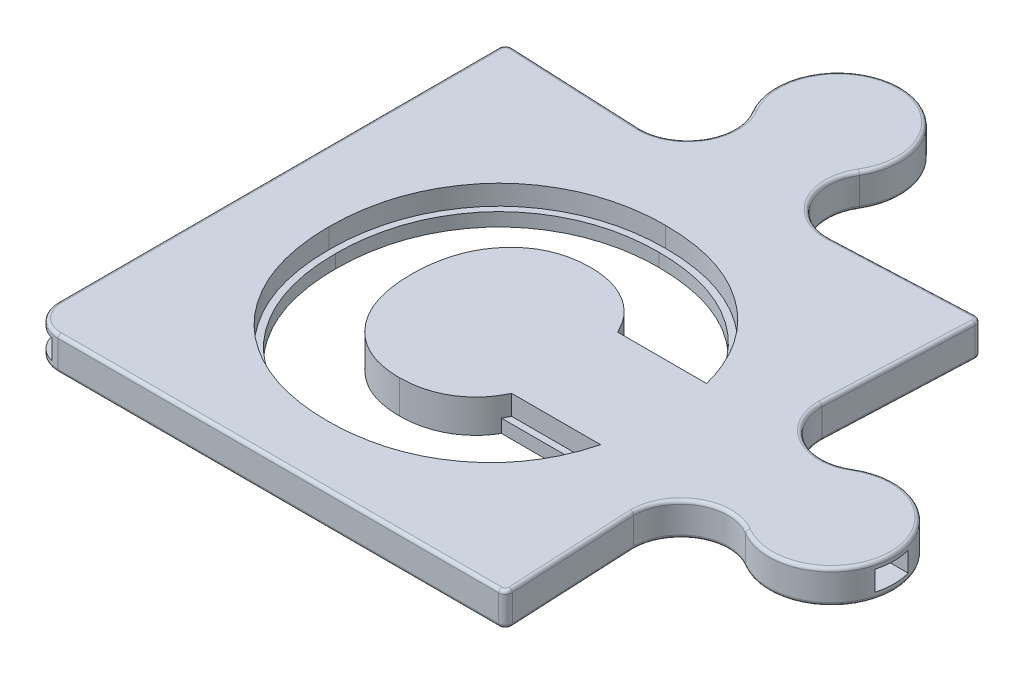
SolidWorks part; units mm, degrees
ref_plane "Front Plane" through (0, 0, 0) normal (0, 0, 1) x (1, 0, 0)
ref_plane "Top Plane" through (0, 0, 0) normal (0, 1, 0) x (1, 0, 0)
ref_plane "Right Plane" through (0, 0, 0) normal (1, 0, 0) x (0, 0, -1)
sketch "Sketch1" plane through (0, 0, 0) normal (0, 1, 0) x (1, 0, 0)
  line L0 (-31, -36) -> (37, -36) construction
  line L1 (-36, 37) -> (-36, -31) construction
  line L2 (-14.1421, 36) -> (-36, 37) construction
  line L3 (37, 37) -> (14.1421, 36) construction
  line L4 (36, 13.1421) -> (37, 37) construction
  line L5 (37, -36) -> (36, -15.1421) construction
  line L6 (-35.4, 36.3719) -> (-35.4, -31)
  line L7 (-36, 36) -> (36, 36) construction
  line L8 (-36, 36) -> (-36, -36) construction
  line L9 (-36, -36) -> (36, -36) construction
  line L10 (36, 36) -> (36, -36) construction
  line L11 (-31, -35.4) -> (36.3705, -35.4)
  line L12 (36.3705, -35.4) -> (35.4, -15.1568)
  line L13 (35.4, 13.155) -> (36.3732, 36.372)
  line L14 (36.3732, 36.372) -> (14.1555, 35.4)
  line L15 (-14.1562, 35.4) -> (-35.4, 36.3719)
  line L16 (-30, -24) -> (30, -24) construction
  line L17 (-30, 29) -> (30, 29) construction
  line L18 (-30, 29) -> (-30, -31) construction
  line L19 (-30, -31) -> (30, -31) construction
  line L20 (30, 29) -> (30, -31) construction
  line L21 (-30, 24) -> (30, 24) construction
  line L22 (-30, 24) -> (-30, -26) construction
  line L23 (-30, -26) -> (30, -26) construction
  line L24 (30, 24) -> (30, -26) construction
  arc A0 (-36, -31) -> (-31, -36) centre (-31, -31) ccw construction
  arc A1 (-14.1421, 36) -> (-8.571, 45.8485) centre (-14.1421, 42.5) ccw construction
  arc A2 (8.571, 45.8485) -> (-8.571, 45.8485) centre (0, 51) ccw construction
  arc A3 (8.571, 45.8485) -> (14.1421, 36) centre (14.1421, 42.5) ccw construction
  arc A4 (36, 13.1421) -> (45.8485, 7.571) centre (42.5, 13.1421) ccw construction
  arc A5 (45.8485, -9.571) -> (45.8485, 7.571) centre (51, -1) ccw construction
  arc A6 (45.8485, -9.571) -> (36, -15.1421) centre (42.5, -15.1421) ccw construction
  arc A7 (-35.4, -31) -> (-31, -35.4) centre (-31, -31) ccw
  arc A8 (46.1576, -9.0567) -> (35.4, -15.1568) centre (42.5, -15.1421) ccw
  arc A9 (46.1576, -9.0567) -> (46.1576, 7.0567) centre (51, -1) ccw
  arc A10 (35.4, 13.155) -> (46.1576, 7.0567) centre (42.5, 13.1421) ccw
  arc A11 (8.0567, 46.1576) -> (14.1555, 35.4) centre (14.1421, 42.5) ccw
  arc A12 (8.0567, 46.1576) -> (-8.0567, 46.1576) centre (0, 51) ccw
  arc A13 (-14.1562, 35.4) -> (-8.0567, 46.1576) centre (-14.1421, 42.5) ccw
  point P32 (36, 0)
  point P34 (0, 36)
  dimension "D5" = 6.5
  dimension "D6" = 10
  dimension "D7" = 6.5
  dimension "D13" = 5
  dimension "D9" = 10
  dimension "D11" = 6.5
  dimension "D12" = 6.5
  dimension "D1" = 72
  dimension "D2" = 1
  dimension "D3" = 1
  dimension "D4" = 15
  dimension "D8" = 1
  dimension "D10" = 35
  dimension "D14" = 15
  dimension "D15" = 36
  dimension "D16" = 1
  dimension "D18" = 60
  dimension "D19" = 60
  dimension "D20" = 5
  dimension "D21" = 6
  dimension "D22" = 5
  dimension "D23" = 50
  dimension "D24" = 2
  dimension "D17" = 0.6
extrude "Boss-Extrude1" add sketch "Sketch1" along normal blind 5
sketch "Sketch6" plane through (0, 0, 0) normal (0, -1, 0) x (1, 0, 0)
  line L0 (-35.4, -36.3719) -> (-35.4, 31) construction
  line L1 (-35.4, 17.9) -> (-27.4, 17.9)
  line L2 (-35.4, 17.9) -> (-35.4, -16.1)
  line L3 (-35.4, -16.1) -> (-27.4, -16.1)
  line L4 (-27.4, 17.9) -> (-27.4, -16.1)
  line L5 (-31, 35.4) -> (36.3705, 35.4) construction
  line L6 (-35.4, 14.65) -> (-30.4, 14.65)
  line L7 (-35.4, 14.65) -> (-35.4, -12.85)
  line L8 (-35.4, -12.85) -> (-30.4, -12.85)
  line L9 (-30.4, 14.65) -> (-30.4, -12.85)
  point P15 (-27.4, 0.9)
  point P16 (-30.4, 0.9)
  line M28 (-35.4, 31) -> (-35.4, -36.3719)
  dimension "D1" = 8
  dimension "D2" = 20.75
  dimension "D3" = 27.5
  dimension "D4" = 5
  dimension "D5" = 34
extrude "Cut-Extrude3" cut sketch "Sketch6" against normal blind 3 from offset 1 contours L6 L9 L8 L3 L4 L1 M28 | L9 L6 L2 L8 region at (-29.8665, 0, 0.9) region at (-32.9, 0, 0.9) offset against normal yes
extrude "Cut-Extrude4" cut sketch "Sketch6<3>" against normal up to next contours L9 L6 L2 L8 region at (-32.9, 0, 0.9)
sketch "Sketch6<3>" plane through (0, 0, 0) normal (0, -1, 0) x (1, 0, 0) same geometry as "Sketch6"
sketch "Sketch8" plane through (0, 0, 0) normal (0, -1, 0) x (1, 0, 0)
  line L1 (-2.5, -51.4) -> (2.5, -51.4)
  line L2 (-2.5, -51.4) -> (-2.5, -60.4)
  line L3 (-2.5, -60.4) -> (2.5, -60.4)
  line L4 (2.5, -51.4) -> (2.5, -60.4)
  line L5 (51.4, 3.5) -> (60.4, 3.5)
  line L6 (51.4, 3.5) -> (51.4, -1.5)
  line L7 (51.4, -1.5) -> (60.4, -1.5)
  line L8 (60.4, 3.5) -> (60.4, -1.5)
  arc A0 (-8.0567, -46.1576) -> (8.0567, -46.1576) centre (0, -51) ccw construction
  arc A1 (46.1576, -7.0567) -> (46.1576, 9.0567) centre (51, 1) ccw construction
  point P4 (0, -60.4)
  point P13 (60.4, 1)
  dimension "D1" = 5
  dimension "D2" = 9
  dimension "D3" = 5
  dimension "D4" = 9
extrude "Cut-Extrude5" cut sketch "Sketch8" against normal blind 3 from offset 1 offset against normal yes
sketch "Sketch9" plane through (0, 0, 0) normal (0, -1, 0) x (1, 0, 0)
  line L0 (-31, 35.4) -> (36.3705, 35.4) construction
  line L1 (-35.4, 14.65) -> (-35.4, 31) construction
  line L2 (-31.7636, 35.3332) -> (-35.4, 31) construction
  line L3 (-33.2571, 29.735) -> (-30.0429, 33.565) construction
  line L4 (-30.0429, 33.565) -> (-33.2571, 29.735) construction
  line L5 (-30.0429, 33.565) -> (-32.7119, 35.8048)
  line L6 (-33.2571, 29.735) -> (-35.926, 31.9747)
  line L7 (-32.7119, 35.8048) -> (-35.926, 31.9747)
  circle A0 centre (-31.65, 31.65) radius 2.5
  arc A1 (-31, 35.4) -> (-35.4, 31) centre (-31, 31) ccw construction
  arc M41 (-31, 35.4) -> (-35.4, 31) centre (-31, 31) ccw
  dimension "D1" = 5
  dimension "D3" = 3.75
  dimension "D4" = 5.6569
  dimension "D2" = 3.75
extrude "Cut-Extrude6" cut sketch "Sketch9" against normal blind 3 from offset 1 contours A0 L5 L6 M41 | A0 L5 region at (-33.6239, 0, 33.3064) region at (-31.65, 0, 31.65) offset against normal yes
sketch "Sketch11" plane through (-35.4, 0, 0) normal (-1, 0, 0) x (0, 0, 1)
  line L0 (-13.155, 0) -> (-36.372, 0) construction
  line L1 (-25.1, 3) -> (-19.1, 3)
  line L2 (-25.1, 3) -> (-25.1, 1.5)
  line L3 (-25.1, 1.5) -> (-19.1, 1.5)
  line L4 (-19.1, 3) -> (-19.1, 1.5)
  line L5 (-16.1, 4) -> (-16.1, 1) construction
  line L6 (35.4, 0) -> (15.1568, 0) construction
  line L7 (20.9, 3) -> (26.9, 3)
  line L8 (20.9, 3) -> (20.9, 1.5)
  line L9 (20.9, 1.5) -> (26.9, 1.5)
  line L10 (26.9, 3) -> (26.9, 1.5)
  line L12 (17.9, 4) -> (17.9, 1) construction
  dimension "D1" = 3
  dimension "D2" = 1.5
  dimension "D3" = 3
  dimension "D4" = 6
  dimension "D5" = 3
  dimension "D6" = 1.5
  dimension "D7" = 6
  dimension "D8" = 3
fillet "Fillet1" radius 0.5 17 edges at (-35.4, 0, 22.825) (-34.1113, 0, 34.1113) (2.6853, 0, 35.4) (35.8853, 0, 25.2784) (38.9978, 0, 8.966) (60.4, 0, 1) (38.9986, 0, -6.9655) (35.8866, 0, -24.7635) (25.2643, 0, -35.886) (7.9657, 0, -38.9984) (0, 0, -60.4) (-7.9658, 0, -38.9981) (-24.7781, 0, -35.886) (-35.4, 0, -24.611) (-32.9, 0, -12.85) (-30.4, 0, 0.9) (-32.9, 0, 14.65)
fillet "Fillet2" radius 0.5 13 edges at (-7.9658, 5, -38.9981) (0, 5, -60.4) (7.9657, 5, -38.9984) (25.2643, 5, -35.886) (35.8866, 5, -24.7635) (38.9986, 5, -6.9655) (60.4, 5, 1) (38.9978, 5, 8.966) (35.8853, 5, 25.2784) (2.6853, 5, 35.4) (-34.1113, 5, 34.1113) (-35.4, 5, -2.686) (-24.7781, 5, -35.886)
fillet "Fillet3" radius 1 9 edges at (36.2202, 0.1464, -36.2187) (36.2202, 4.8536, -36.2187) (36.3732, 2.5, -36.372) (-35.2536, 0.1464, -36.2186) (-35.2536, 4.8536, -36.2186) (36.2169, 0.1464, 35.2536) (36.2169, 4.8536, 35.2536) (36.3705, 2.5, 35.4) (-35.4, 2.5, -36.3719)
extrude "Cut-Extrude9" cut sketch "Sketch11" against normal blind 3
chamfer "Chamfer1" distance 1 angle 50 2 edges at (-35.4, 1.5, 23.9) (-35.4, 1.5, -22.1) first distance on face at (-35.4, 2.25, -22.1)
sketch "Sketch12" plane through (0, 5, 0) normal (0, 1, 0) x (1, 0, 0)
  text T0 "C" font "Poppins" height 50
extrude "Cut-Extrude10" cut sketch "Sketch12" against normal through all
sketch "Sketch13" plane through (0, 0, 0) normal (0, -1, 0) x (1, 0, 0)
  line L0 (23.2135, -6.7755) -> (24.1756, -7.0482)
  line L1 (10.2401, -8.0482) -> (24.1756, -8.0482)
  line L2 (10.2401, -8.0482) -> (10.2401, -7.0482)
  line L3 (10.2401, -7.0482) -> (24.1756, -7.0482)
  line L4 (24.1756, -8.0482) -> (24.1756, -7.0482)
  line L5 (10.2401, 9.904) -> (24.1756, 9.904)
  line L6 (10.2401, 9.904) -> (10.2401, 8.904)
  line L7 (10.2401, 8.904) -> (24.1756, 8.904)
  line L8 (24.1756, 9.904) -> (24.1756, 8.904)
  line L9 (23.2135, 8.6313) -> (24.1756, 8.904)
  spline S0 degree 3 poles (10.7791, -7.0482) (10.5182, -7.5478) (10.0072, -8.5259) (9.0157, -9.8304) (7.855, -10.9302) (6.561, -11.8562) (5.1388, -12.5768) (3.6098, -13.0821) (1.9919, -13.4026) (0.8775, -13.4393) (0.3092, -13.458) knots 0 0 0 0 0.129974 0.254511 0.376256 0.497972 0.620713 0.742871 0.868879 1 1 1 1 construction
  spline S1 degree 3 poles (0.3092, 15.3137) (0.8775, 15.295) (1.9919, 15.2583) (3.6098, 14.9379) (5.1388, 14.4325) (6.561, 13.7119) (7.855, 12.786) (9.0157, 11.6861) (10.0072, 10.3817) (10.5182, 9.4035) (10.7791, 8.904) knots 0 0 0 0 0.131121 0.257129 0.379287 0.502028 0.623744 0.745489 0.870026 1 1 1 1 construction
  spline S12 degree 3 poles (17.1448, -4021.034) (-113.3486, 50.2289) (-32.4673, -25.5536) (2.7213, -23.4991) (3.0371, -23.4735) (3.6731, -23.4095) (3.9919, -23.3714) (4.9509, -23.2421) (5.5885, -23.1391) (6.8387, -22.8863) (7.4555, -22.7345) (8.6742, -22.3764) (9.2756, -22.1695) (10.4681, -21.7075) (11.0567, -21.4553) (12.1956, -20.9031) (12.75, -20.599) (13.8417, -19.94) (14.3756, -19.5886) (15.9211, -18.4727) (16.8859, -17.638) (18.6494, -15.813) (19.4442, -14.8216) (20.4973, -13.2331) (20.8248, -12.6885) (21.4294, -11.5724) (21.7078, -10.9986) (22.2206, -9.8288) (22.4522, -9.2381) (33.2049, 22.7753) (-22.2019, 121.8896) (3885.5781, -1037.5135) knots -3.367149 -3.367149 -3.367149 -3.367149 0.0625 0.0625 0.09375 0.09375 0.125 0.125 0.1875 0.1875 0.25 0.25 0.3125 0.3125 0.375 0.375 0.4375 0.4375 0.5 0.5 0.625 0.625 0.75 0.75 0.8125 0.8125 0.875 0.875 0.9375 0.9375 4.212647 4.212647 4.212647 4.212647 only from (0.4529, -23.577) to (23.2135, -6.7755)
  spline S13 degree 3 poles (3884.4434, 1043.6961) (-22.1974, -120.0983) (33.1908, -20.8772) (22.4532, 11.0907) (22.2218, 11.6806) (21.71, 12.8502) (21.433, 13.4234) (20.8297, 14.5337) (20.5004, 15.0759) (19.4428, 16.6652) (18.6531, 17.6582) (17.3332, 19.0179) (16.8699, 19.4516) (15.9064, 20.2784) (15.4072, 20.6704) (14.3754, 21.4091) (13.8417, 21.7569) (12.7483, 22.4082) (12.19, 22.7101) (11.048, 23.2628) (10.4628, 23.5151) (9.2752, 23.9707) (8.6753, 24.1721) (7.4547, 24.5204) (6.8307, 24.6699) (5.5743, 24.9297) (4.944, 25.0381) (3.6783, 25.2059) (3.0443, 25.2653) (-34.2641, 27.3144) (-113.5748, -44.6835) (-30.8433, 4022.5945) knots -3.212629 -3.212629 -3.212629 -3.212629 0.0625 0.0625 0.125 0.125 0.1875 0.1875 0.25 0.25 0.375 0.375 0.4375 0.4375 0.5 0.5 0.5625 0.5625 0.625 0.625 0.6875 0.6875 0.75 0.75 0.8125 0.8125 0.875 0.875 0.9375 0.9375 4.525891 4.525891 4.525891 4.525891 only from (23.2135, 8.6313) to (0.4518, 25.3605)
  spline S14 degree 3 poles (-4020.2474, 81.6617) (20.4498, 112.5508) (-24.8624, 36.1709) (-23.6486, -0.7197) (-23.6289, -1.1224) (-23.5407, -2.328) (-23.4421, -3.1218) (-23.1708, -4.7169) (-23.0037, -5.5137) (-22.7048, -6.6839) (-22.5966, -7.0688) (-22.358, -7.8278) (-22.2263, -8.206) (-21.9437, -8.9604) (-21.7935, -9.3366) (-21.4779, -10.0755) (-21.3118, -10.4387) (-20.7819, -11.5157) (-20.3887, -12.2171) (-19.5354, -13.58) (-19.0777, -14.2385) (-18.0919, -15.5017) (-17.5654, -16.1136) (-16.7358, -16.9645) (-16.4492, -17.2392) (-15.8567, -17.7758) (-15.5517, -18.0375) (-14.6188, -18.798) (-13.9722, -19.2744) (-12.635, -20.1438) (-11.9345, -20.5453) (-10.5053, -21.2784) (-9.7741, -21.6079) (-8.2805, -22.1864) (-7.5191, -22.4343) (-6.3522, -22.7539) (-5.9587, -22.8529) (-5.1744, -23.0313) (-4.7841, -23.11) (-3.9968, -23.2441) (-3.5978, -23.3006) (-2.7911, -23.3999) (-2.3856, -23.4435) (-1.5826, -23.5118) (-1.1862, -23.5353) (32.0867, -24.7145) (110.5026, 25.6422) (12.2193, -4021.2419) knots -2.76164 -2.76164 -2.76164 -2.76164 0.03125 0.03125 0.0625 0.0625 0.125 0.125 0.1875 0.1875 0.21875 0.21875 0.25 0.25 0.28125 0.28125 0.3125 0.3125 0.375 0.375 0.4375 0.4375 0.5 0.5 0.53125 0.53125 0.5625 0.5625 0.625 0.625 0.6875 0.6875 0.75 0.75 0.8125 0.8125 0.84375 0.84375 0.875 0.875 0.90625 0.90625 0.9375 0.9375 0.96875 0.96875 3.506794 3.506794 3.506794 3.506794 only from (-23.6907, 0.9279) to (0.4529, -23.577)
  spline S15 degree 3 poles (11.912, 4022.9128) (110.504, -23.8319) (32.0857, 26.4974) (-1.1849, 25.3189) (-1.5807, 25.2955) (-2.3825, 25.2274) (-2.7874, 25.1839) (-3.593, 25.0848) (-3.9914, 25.0285) (-4.7775, 24.8949) (-5.1672, 24.8163) (-5.9505, 24.6384) (-6.3439, 24.5397) (-7.1206, 24.3275) (-7.504, 24.2133) (-8.2635, 23.9639) (-8.6411, 23.8287) (-9.3921, 23.54) (-9.7645, 23.3873) (-10.4962, 23.0645) (-10.8556, 22.8941) (-11.9204, 22.3502) (-12.6084, 21.9454) (-13.6223, 21.2853) (-13.9551, 21.0588) (-14.6024, 20.5917) (-14.9167, 20.3504) (-15.5354, 19.8464) (-15.8399, 19.5842) (-16.4327, 19.0472) (-16.7204, 18.7723) (-17.2767, 18.2061) (-17.5474, 17.9131) (-18.0753, 17.3109) (-18.3323, 17.0027) (-18.8256, 16.3763) (-19.0614, 16.0576) (-19.5189, 15.4018) (-19.7409, 15.065) (-20.385, 14.0425) (-20.7814, 13.3455) (-21.3117, 12.2743) (-21.4769, 11.9133) (-21.7918, 11.1756) (-21.9423, 10.7983) (-22.2267, 10.044) (-22.3593, 9.6671) (-22.5977, 8.9123) (-22.7052, 8.5285) (-22.904, 7.7489) (-22.9959, 7.3534) (-23.164, 6.5624) (-23.2402, 6.1652) (-23.4433, 4.9725) (-23.541, 4.179) (-23.629, 2.975) (-23.6488, 2.573) (-24.8601, -34.2725) (20.4442, -110.6927) (-4020.4503, -76.7471) knots -2.510374 -2.510374 -2.510374 -2.510374 0.03125 0.03125 0.0625 0.0625 0.09375 0.09375 0.125 0.125 0.15625 0.15625 0.1875 0.1875 0.21875 0.21875 0.25 0.25 0.28125 0.28125 0.3125 0.3125 0.375 0.375 0.40625 0.40625 0.4375 0.4375 0.46875 0.46875 0.5 0.5 0.53125 0.53125 0.5625 0.5625 0.59375 0.59375 0.625 0.625 0.6875 0.6875 0.71875 0.71875 0.75 0.75 0.78125 0.78125 0.8125 0.8125 0.84375 0.84375 0.875 0.875 0.9375 0.9375 0.96875 0.96875 3.762508 3.762508 3.762508 3.762508 only from (0.4518, 25.3605) to (-23.6907, 0.9279)
  spline S16 degree 3 poles (0.4529, -23.577) (1.1174, -23.566) (1.7681, -23.5547) (2.7213, -23.4991) (3.0371, -23.4735) (3.6731, -23.4095) (3.9919, -23.3714) (4.9509, -23.2421) (5.5885, -23.1391) (6.8387, -22.8863) (7.4555, -22.7345) (8.6742, -22.3764) (9.2756, -22.1695) (10.4681, -21.7075) (11.0567, -21.4553) (12.1956, -20.9031) (12.75, -20.599) (13.8417, -19.94) (14.3756, -19.5886) (15.9211, -18.4727) (16.8859, -17.638) (18.6494, -15.813) (19.4442, -14.8216) (20.4973, -13.2331) (20.8248, -12.6885) (21.4294, -11.5724) (21.7078, -10.9986) (22.2206, -9.8288) (22.4522, -9.2381) (22.8549, -8.0392) (23.0322, -7.415) (23.2135, -6.7755) knots 0 0 0 0 0.0625 0.0625 0.09375 0.09375 0.125 0.125 0.1875 0.1875 0.25 0.25 0.3125 0.3125 0.375 0.375 0.4375 0.4375 0.5 0.5 0.625 0.625 0.75 0.75 0.8125 0.8125 0.875 0.875 0.9375 0.9375 1 1 1 1
  spline S17 degree 3 poles (23.2135, 8.6313) (23.0324, 9.2701) (22.8554, 9.8934) (22.4532, 11.0907) (22.2218, 11.6806) (21.71, 12.8502) (21.433, 13.4234) (20.8297, 14.5337) (20.5004, 15.0759) (19.4428, 16.6652) (18.6531, 17.6582) (17.3332, 19.0179) (16.8699, 19.4516) (15.9064, 20.2784) (15.4072, 20.6704) (14.3754, 21.4091) (13.8417, 21.7569) (12.7483, 22.4082) (12.19, 22.7101) (11.048, 23.2628) (10.4628, 23.5151) (9.2752, 23.9707) (8.6753, 24.1721) (7.4547, 24.5204) (6.8307, 24.6699) (5.5743, 24.9297) (4.944, 25.0381) (3.6783, 25.2059) (3.0443, 25.2653) (1.7669, 25.3355) (1.1153, 25.3481) (0.4518, 25.3605) knots 0 0 0 0 0.0625 0.0625 0.125 0.125 0.1875 0.1875 0.25 0.25 0.375 0.375 0.4375 0.4375 0.5 0.5 0.5625 0.5625 0.625 0.625 0.6875 0.6875 0.75 0.75 0.8125 0.8125 0.875 0.875 0.9375 0.9375 1 1 1 1
  spline S18 degree 3 poles (-23.6907, 0.9279) (-23.6831, 0.5099) (-23.6755, 0.0967) (-23.6486, -0.7197) (-23.6289, -1.1224) (-23.5407, -2.328) (-23.4421, -3.1218) (-23.1708, -4.7169) (-23.0037, -5.5137) (-22.7048, -6.6839) (-22.5966, -7.0688) (-22.358, -7.8278) (-22.2263, -8.206) (-21.9437, -8.9604) (-21.7935, -9.3366) (-21.4779, -10.0755) (-21.3118, -10.4387) (-20.7819, -11.5157) (-20.3887, -12.2171) (-19.5354, -13.58) (-19.0777, -14.2385) (-18.0919, -15.5017) (-17.5654, -16.1136) (-16.7358, -16.9645) (-16.4492, -17.2392) (-15.8567, -17.7758) (-15.5517, -18.0375) (-14.6188, -18.798) (-13.9722, -19.2744) (-12.635, -20.1438) (-11.9345, -20.5453) (-10.5053, -21.2784) (-9.7741, -21.6079) (-8.2805, -22.1864) (-7.5191, -22.4343) (-6.3522, -22.7539) (-5.9587, -22.8529) (-5.1744, -23.0313) (-4.7841, -23.11) (-3.9968, -23.2441) (-3.5978, -23.3006) (-2.7911, -23.3999) (-2.3856, -23.4435) (-1.5826, -23.5118) (-1.1862, -23.5353) (-0.3768, -23.564) (0.0348, -23.5705) (0.4529, -23.577) knots 0 0 0 0 0.03125 0.03125 0.0625 0.0625 0.125 0.125 0.1875 0.1875 0.21875 0.21875 0.25 0.25 0.28125 0.28125 0.3125 0.3125 0.375 0.375 0.4375 0.4375 0.5 0.5 0.53125 0.53125 0.5625 0.5625 0.625 0.625 0.6875 0.6875 0.75 0.75 0.8125 0.8125 0.84375 0.84375 0.875 0.875 0.90625 0.90625 0.9375 0.9375 0.96875 0.96875 1 1 1 1
  spline S19 degree 3 poles (0.4518, 25.3605) (0.0343, 25.3541) (-0.3767, 25.3475) (-1.1849, 25.3189) (-1.5807, 25.2955) (-2.3825, 25.2274) (-2.7874, 25.1839) (-3.593, 25.0848) (-3.9914, 25.0285) (-4.7775, 24.8949) (-5.1672, 24.8163) (-5.9505, 24.6384) (-6.3439, 24.5397) (-7.1206, 24.3275) (-7.504, 24.2133) (-8.2635, 23.9639) (-8.6411, 23.8287) (-9.3921, 23.54) (-9.7645, 23.3873) (-10.4962, 23.0645) (-10.8556, 22.8941) (-11.9204, 22.3502) (-12.6084, 21.9454) (-13.6223, 21.2853) (-13.9551, 21.0588) (-14.6024, 20.5917) (-14.9167, 20.3504) (-15.5354, 19.8464) (-15.8399, 19.5842) (-16.4327, 19.0472) (-16.7204, 18.7723) (-17.2767, 18.2061) (-17.5474, 17.9131) (-18.0753, 17.3109) (-18.3323, 17.0027) (-18.8256, 16.3763) (-19.0614, 16.0576) (-19.5189, 15.4018) (-19.7409, 15.065) (-20.385, 14.0425) (-20.7814, 13.3455) (-21.3117, 12.2743) (-21.4769, 11.9133) (-21.7918, 11.1756) (-21.9423, 10.7983) (-22.2267, 10.044) (-22.3593, 9.6671) (-22.5977, 8.9123) (-22.7052, 8.5285) (-22.904, 7.7489) (-22.9959, 7.3534) (-23.164, 6.5624) (-23.2402, 6.1652) (-23.4433, 4.9725) (-23.541, 4.179) (-23.629, 2.975) (-23.6488, 2.573) (-23.6756, 1.7578) (-23.6831, 1.3453) (-23.6907, 0.9279) knots 0 0 0 0 0.03125 0.03125 0.0625 0.0625 0.09375 0.09375 0.125 0.125 0.15625 0.15625 0.1875 0.1875 0.21875 0.21875 0.25 0.25 0.28125 0.28125 0.3125 0.3125 0.375 0.375 0.40625 0.40625 0.4375 0.4375 0.46875 0.46875 0.5 0.5 0.53125 0.53125 0.5625 0.5625 0.59375 0.59375 0.625 0.625 0.6875 0.6875 0.71875 0.71875 0.75 0.75 0.78125 0.78125 0.8125 0.8125 0.84375 0.84375 0.875 0.875 0.9375 0.9375 0.96875 0.96875 1 1 1 1
  spline M30 degree 3 poles (-24.6908, 0.9279) (-24.6799, 1.5361) (-24.6581, 2.7405) (-24.5181, 4.5211) (-24.2554, 6.2473) (-23.9029, 7.9222) (-23.4699, 9.5526) (-22.9009, 11.1232) (-22.2598, 12.6501) (-21.5036, 14.1147) (-20.6575, 15.5115) (-19.744, 16.8468) (-18.7403, 18.0927) (-17.6675, 19.2648) (-16.5057, 20.348) (-15.2702, 21.3621) (-13.945, 22.2857) (-12.5567, 23.1451) (-11.1005, 23.9048) (-9.5853, 24.5534) (-8.0312, 25.113) (-6.4252, 25.5633) (-4.7756, 25.932) (-3.0727, 26.1683) (-1.3257, 26.3332) (-0.1447, 26.3514) (0.4534, 26.3607) knots 0 0 0 0 0.045484 0.090067 0.133442 0.175961 0.218022 0.259456 0.300773 0.341786 0.382579 0.422836 0.462671 0.502119 0.541554 0.58135 0.621543 0.66225 0.703381 0.744226 0.785418 0.826806 0.868877 0.911706 0.955287 1 1 1 1
  spline M31 degree 3 poles (0.4534, 26.3607) (1.1821, 26.347) (2.6154, 26.3202) (4.7281, 26.102) (6.7583, 25.7269) (8.7162, 25.229) (10.5861, 24.5641) (12.3762, 23.7597) (14.0839, 22.8045) (15.7064, 21.7189) (17.2227, 20.501) (18.6198, 19.1705) (19.8796, 17.7228) (21.0054, 16.168) (22.013, 14.5142) (22.8745, 12.7457) (23.6174, 10.8733) (23.9876, 9.5672) (24.1756, 8.904) knots 0 0 0 0 0.068588 0.1349 0.199656 0.26279 0.324868 0.38623 0.447317 0.508839 0.569791 0.630169 0.690215 0.750171 0.810673 0.872277 0.935146 1 1 1 1
  spline M38 degree 3 poles (24.1756, -7.0482) (23.9876, -7.7114) (23.6173, -9.0175) (22.875, -10.8902) (22.01, -12.66) (21.0086, -14.3211) (19.8796, -15.8776) (18.6168, -17.3254) (17.2233, -18.666) (15.7067, -19.8941) (14.0838, -20.989) (12.3792, -21.9577) (10.5838, -22.7576) (8.7167, -23.434) (6.761, -23.9501) (4.726, -24.3002) (2.6164, -24.5413) (1.1823, -24.565) (0.4534, -24.5771) knots 0 0 0 0 0.064776 0.127569 0.189099 0.249803 0.309687 0.369661 0.430189 0.491271 0.552899 0.614069 0.675358 0.737469 0.800609 0.865229 0.931495 1 1 1 1
  spline M39 degree 3 poles (0.4534, -24.5771) (-0.1447, -24.5678) (-1.3257, -24.5496) (-3.0727, -24.3847) (-4.7756, -24.1483) (-6.4253, -23.7799) (-8.0308, -23.3286) (-9.5878, -22.7723) (-11.0985, -22.1093) (-12.5533, -21.3494) (-13.9515, -20.505) (-15.2666, -19.5664) (-16.506, -18.5546) (-17.6705, -17.4702) (-18.7405, -16.2883) (-19.7408, -15.0332) (-20.6608, -13.6956) (-21.5035, -12.2895) (-22.2572, -10.8172) (-22.9036, -9.2856) (-23.4675, -7.7097) (-23.9048, -6.0738) (-24.254, -4.3947) (-24.5184, -2.6654) (-24.658, -0.8847) (-24.6798, 0.3197) (-24.6908, 0.9279) knots 0 0 0 0 0.044649 0.088167 0.130934 0.172943 0.214271 0.255404 0.296292 0.337363 0.377877 0.41816 0.4579 0.497277 0.536857 0.576835 0.617034 0.657987 0.699169 0.740426 0.782043 0.824043 0.866752 0.910064 0.954582 1 1 1 1
  dimension "D1" = 1
  dimension "D2" = 1
  dimension "D3" = 1
extrude "Boss-Extrude2" add sketch "Sketch13" against normal blind 2 contours S19 S17 L5 L1 S16 S18 M31 M30 M39 M38 | L4 L1 L2 L3 | L8 L5 L6 L7 region at (16.9338, 0, -18.5052) region at (3.0477, 0, -24.0798) region at (-24.1896, 0, 0.9289) region at (-23.7573, 0, 3.6891) region at (3.0987, 0, 25.4374)
